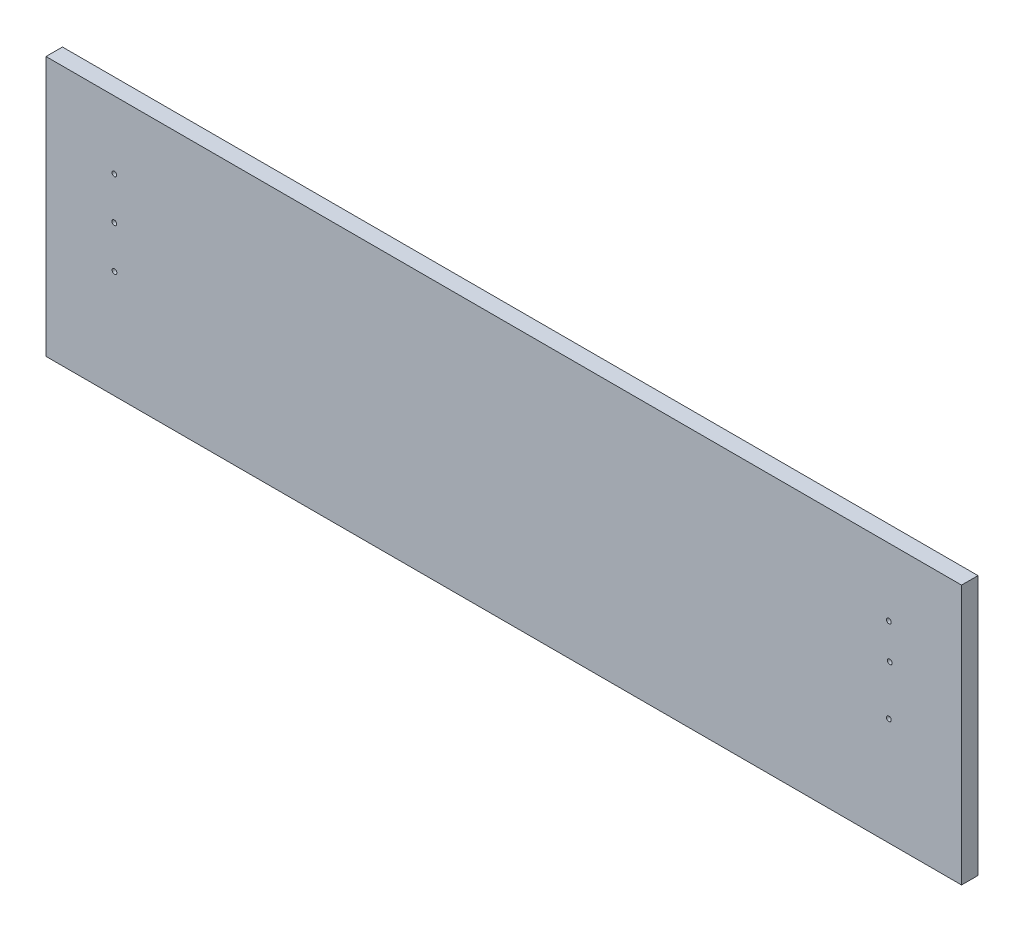
SolidWorks part; units mm, degrees
ref_plane "Front Plane" through (0, 0, 0) normal (0, 0, 1) x (1, 0, 0)
ref_plane "Top Plane" through (0, 0, 0) normal (0, 1, 0) x (1, 0, 0)
ref_plane "Right Plane" through (0, 0, 0) normal (1, 0, 0) x (0, 0, -1)
sketch "Sketch1" plane through (0, 0, 0) normal (0, 0, 1) x (1, 0, 0)
  line L0 (-1881.9192, 653.736) -> (-824.4592, 653.736) construction
  line L1 (-1881.9192, 503.736) -> (-824.4592, 503.736)
  line L2 (-1881.9192, 503.736) -> (-1881.9192, 803.736)
  line L3 (-1881.9192, 803.736) -> (-824.4592, 803.736)
  line L4 (-824.4592, 503.736) -> (-824.4592, 803.736)
  line L5 (-1353.1892, 653.736) -> (-1353.1892, 503.736) construction
  line L6 (-928.1289, 703.236) -> (-1785.9199, 703.236) construction
  line L7 (-928.1289, 703.236) -> (-1785.9199, 703.236) construction
  dimension "D1" = 1057.46
  dimension "D2" = 300
extrude "Boss-Extrude1" add sketch "Sketch1" along normal blind 19
sketch "Sketch2" plane through (0, 0, 0) normal (0, 0, -1) x (-1, 0, 0)
  line L0 (887.3199, 576.496) -> (966.4873, 576.506) construction
  line L1 (887.3199, 576.496) -> (887.3199, 714.236) construction
  line L2 (887.3199, 714.236) -> (942.25, 714.236)
  point P0 (907.3199, 694.236)
  point P1 (907.3199, 643.1464)
  point P2 (907.3199, 596.4985)
  dimension "D1" = 20
  dimension "D2" = 20
  dimension "D3" = 20
sketch "Sketch7" plane through (0, 0, 0) normal (0, 0, -1) x (-1, 0, 0)
  line L0 (926.5757, 714.236) -> (887.3199, 714.236) construction
  line L1 (887.3199, 714.236) -> (887.3099, 576.506) construction
  line L2 (887.3099, 576.506) -> (916.3736, 576.506) construction
  line L3 (1760.6398, 576.506) -> (1824.3378, 576.506) construction
  line L4 (1824.3378, 576.506) -> (1824.3378, 713.069) construction
  line L5 (1824.3378, 713.069) -> (1760.6291, 713.069) construction
  point P3 (907.3113, 596.506)
  point P5 (907.3113, 645.371)
  point P6 (907.3113, 694.236)
  point P8 (887.3149, 645.371)
  point P12 (1803.6883, 596.506)
  point P13 (1811.0963, 644.7875)
  point P14 (1804.0368, 693.069)
  point P15 (1824.3378, 644.7875)
  dimension "D1" = 20
  dimension "D2" = 20
  dimension "D3" = 20
  dimension "D4" = 20
  dimension "D5" = 20
hole_wizard "M5 Clearance Hole1" positions "Sketch9" profile "Sketch10" hole size "M5" standard "ISO"
sketch "Sketch9" plane through (-1422.5167, 243.8371, 0) normal (0, 0, -1) x (1, 0, 0)
  point P12 (515.1954, -441.7588)
  point P18 (100.2351, -718.9325)
  point P20 (-182.4777, -714.0157)
  point P21 (514.1117, -481.9429)
  point P23 (514.1117, -384.2129)
  point P25 (-380.5099, -481.9429)
  point P27 (-380.5099, -433.0775)
  point P29 (-380.3331, -384.4382)
  point P34 (0, 0)
  point P35 (0, 0)
  point P36 (0, 0)
  point P37 (0, 0)
  point P38 (0, 0)
sketch "Sketch10" plane through (-907.3213, 685.5959, 0) normal (1, 0, 0) x (0, 1, 0)
  line L0 (0, 0) -> (0, 34)
  line L1 (0, 34) -> (2.75, 32.3476)
  line L2 (2.75, 32.3476) -> (2.75, 0)
  line L3 (2.75, 0) -> (0, 0)
  line L4 (0, 34) -> (-2.75, 32.3476) construction
  line L5 (0, -6.35) -> (0, 107.95) construction
  dimension "Hole Dia." = 5.5
  dimension "Hole Depth" = 34
  dimension "Drill Angle" = 118
